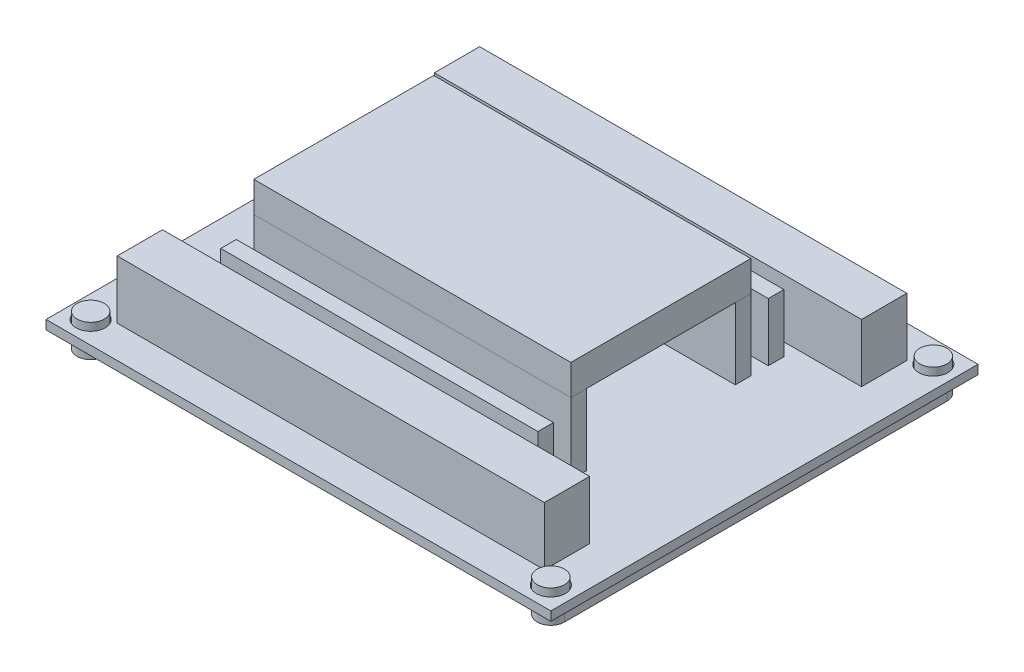
SolidWorks part; units mm, degrees
other "ESP32"
other "ESP32-breadboard"
other "Chassis"
ref_plane "Front Plane" through (0, 0, 0) normal (0, 0, 1) x (1, 0, 0)
ref_plane "Top Plane" through (0, 0, 0) normal (0, 1, 0) x (1, 0, 0)
ref_plane "Right Plane" through (0, 0, 0) normal (1, 0, 0) x (0, 0, -1)
sketch "Sketch1" plane through (0, 0, 0) normal (0, 1, 0) x (1, 0, 0)
  line L1 (-34.7368, 14.7368) -> (43.2632, 14.7368)
  line L2 (-34.7368, 14.7368) -> (-34.7368, -51.2632)
  line L3 (-34.7368, -51.2632) -> (43.2632, -51.2632)
  line L4 (43.2632, 14.7368) -> (43.2632, -51.2632)
  dimension "D1" = 78
  dimension "D2" = 66
extrude "Boss-Extrude1" add sketch "Sketch1" along normal blind 1.4
sketch "Sketch2" plane through (0, 1.4, 0) normal (0, 1, 0) x (1, 0, 0)
  line L0 (43.2632, 14.7368) -> (-34.7368, 14.7368) construction
  line L1 (-28.7368, 9.7368) -> (37.2632, 9.7368)
  line L2 (-28.7368, 9.7368) -> (-28.7368, 2.7368)
  line L3 (-28.7368, 2.7368) -> (37.2632, 2.7368)
  line L4 (37.2632, 9.7368) -> (37.2632, 2.7368)
  line L6 (43.2632, -51.2632) -> (43.2632, 14.7368) construction
  line L7 (-34.7368, 14.7368) -> (-34.7368, -51.2632) construction
  line L8 (-34.7368, -18.2632) -> (43.2632, -18.2632) construction
  line L9 (-28.7368, -39.2632) -> (37.2632, -39.2632)
  line L10 (37.2632, -46.2632) -> (37.2632, -39.2632)
  line L11 (-28.7368, -46.2632) -> (37.2632, -46.2632)
  line L12 (-28.7368, -46.2632) -> (-28.7368, -39.2632)
  line L13 (-21.7368, -34.8632) -> (27.2632, -34.8632)
  line L14 (-21.7368, 0.7368) -> (27.2632, 0.7368)
  line L15 (-21.7368, 0.7368) -> (-21.7368, -1.6632)
  line L16 (-21.7368, -1.6632) -> (27.2632, -1.6632)
  line L17 (27.2632, 0.7368) -> (27.2632, -1.6632)
  line L18 (27.2632, -37.2632) -> (27.2632, -34.8632)
  line L19 (-21.7368, -37.2632) -> (27.2632, -37.2632)
  line L20 (-21.7368, -37.2632) -> (-21.7368, -34.8632)
  line L21 (-34.7368, -3.0132) -> (43.2632, -3.0132) construction
  line L22 (-21.7368, -4.3632) -> (27.2632, -4.3632)
  line L23 (27.2632, -6.7632) -> (27.2632, -4.3632)
  line L24 (-21.7368, -6.7632) -> (27.2632, -6.7632)
  line L25 (-21.7368, -6.7632) -> (-21.7368, -4.3632)
  line L26 (-21.7368, -29.7632) -> (-21.7368, -32.1632)
  line L27 (-21.7368, -29.7632) -> (27.2632, -29.7632)
  line L28 (27.2632, -29.7632) -> (27.2632, -32.1632)
  line L29 (-21.7368, -32.1632) -> (27.2632, -32.1632)
  dimension "D1" = 5
  dimension "D2" = 6
  dimension "D3" = 6
  dimension "D4" = 7
  dimension "D5" = 13
  dimension "D6" = 16
  dimension "D7" = 2.4
  dimension "D8" = 2
  dimension "D9" = 1.35
extrude "Boss-Extrude2" add sketch "Sketch2" along normal blind 9 contours L17 L14 L15 L16 | L20 L19 L18 L13 | L9 L10 L11 L12 | L2 L1 L4 L3 region at (2.7632, 1.4, 36.0632) region at (2.7632, 1.4, 0.4632)
extrude "Boss-Extrude3" add sketch "Sketch2<4>" along normal blind 11 contours L25 L24 L23 L22 | L26 L29 L28 L27 region at (2.7632, 1.4, 5.5632) region at (2.7632, 1.4, 30.9632)
sketch "Sketch2<4>" plane through (0, 1.4, 0) normal (0, 1, 0) x (1, 0, 0) same geometry as "Sketch2"
extrude "Boss-Extrude6" add sketch "Sketch2<5>" against normal blind 2
sketch "Sketch2<5>" plane through (0, 1.4, 0) normal (0, 1, 0) x (1, 0, 0) same geometry as "Sketch2"
sketch "Sketch5" plane through (0, 1.4, 0) normal (0, 1, 0) x (1, 0, 0)
  line L1 (43.2632, 14.7368) -> (-34.7368, 14.7368) construction
  line L2 (-34.7368, 14.7368) -> (-34.7368, -51.2632) construction
  line L3 (4.2632, 14.7368) -> (4.2632, -51.2632) construction
  line L4 (-34.7368, -51.2632) -> (43.2632, -51.2632) construction
  line L5 (-34.7368, -18.2632) -> (43.2632, -18.2632) construction
  line L6 (43.2632, -51.2632) -> (43.2632, 14.7368) construction
  circle A0 centre (-31.2868, 11.2868) radius 2.25
  circle A1 centre (39.8132, 11.2868) radius 2.25
  circle A2 centre (39.8132, -47.8132) radius 2.25
  circle A3 centre (-31.2868, -47.8132) radius 2.25
  dimension "D1" = 4.5
  dimension "D2" = 3.45
  dimension "D3" = 3.45
extrude "Cut-Extrude1" cut sketch "Sketch5" against normal blind 2
sketch "Sketch4" plane through (0, 12.4, 0) normal (0, 1, 0) x (1, 0, 0)
  line L1 (-21.7368, -4.3632) -> (27.2632, -4.3632)
  line L2 (-21.7368, -4.3632) -> (-21.7368, -32.1632)
  line L3 (-21.7368, -32.1632) -> (27.2632, -32.1632)
  line L4 (27.2632, -4.3632) -> (27.2632, -32.1632)
extrude "ESP32" add sketch "Sketch4" along normal blind 4.7 separate body
sketch "Sketch6" plane through (0, 0, 0) normal (0, -1, 0) x (1, 0, 0)
  line L0 (-34.7368, 18.2632) -> (43.2632, 18.2632) construction
  line L1 (-34.7368, -14.7368) -> (-34.7368, 51.2632) construction
  line L2 (43.2632, 51.2632) -> (43.2632, -14.7368) construction
  line L3 (4.2632, 51.2632) -> (4.2632, -14.7368) construction
  line L4 (-34.7368, 51.2632) -> (43.2632, 51.2632) construction
  line L5 (43.2632, -14.7368) -> (-34.7368, -14.7368) construction
  line L6 (-33.3868, 47.8132) -> (-33.3868, -11.2868)
  line L7 (-29.1868, 47.8132) -> (-29.1868, 22.2632)
  line L8 (37.7132, 47.8132) -> (37.7132, 22.2632)
  line L9 (41.9132, 47.8132) -> (41.9132, -11.2868)
  line L10 (37.7132, 14.2632) -> (37.7132, -11.2868)
  line L12 (-29.1868, 14.2632) -> (37.7132, 14.2632)
  line L13 (-29.1868, 22.2632) -> (37.7132, 22.2632)
  line L14 (-29.1868, 14.2632) -> (-29.1868, -11.2868)
  arc A0 (-29.1868, 47.8132) -> (-33.3868, 47.8132) centre (-31.2868, 47.8132) ccw
  arc A1 (37.7132, 47.8132) -> (41.9132, 47.8132) centre (39.8132, 47.8132) cw
  arc A2 (37.7132, -11.2868) -> (41.9132, -11.2868) centre (39.8132, -11.2868) ccw
  arc A3 (-29.1868, -11.2868) -> (-33.3868, -11.2868) centre (-31.2868, -11.2868) cw
  circle A4 centre (-31.2868, -11.2868) radius 2.1
  circle A5 centre (39.8132, -11.2868) radius 2.1
  circle A6 centre (39.8132, 47.8132) radius 2.1
  circle A7 centre (-31.2868, 47.8132) radius 2.1
  dimension "D1" = 4.2
  dimension "D2" = 8
extrude "Boss-Extrude7" add sketch "Sketch6" along normal blind 2.5 separate body contours L8 L13 L7 A0 L6 A3 L14 L12 L10 A2 L9 A1
extrude "Boss-Extrude8" add sketch "Sketch6<3>" against normal blind 2.5 separate body contours A7 | A4 | A5 | A6
sketch "Sketch6<3>" plane through (0, 0, 0) normal (0, -1, 0) x (1, 0, 0) same geometry as "Sketch6"
combine bodies "Combine1" operation type add bodies to combine 108 110 111 112 113
